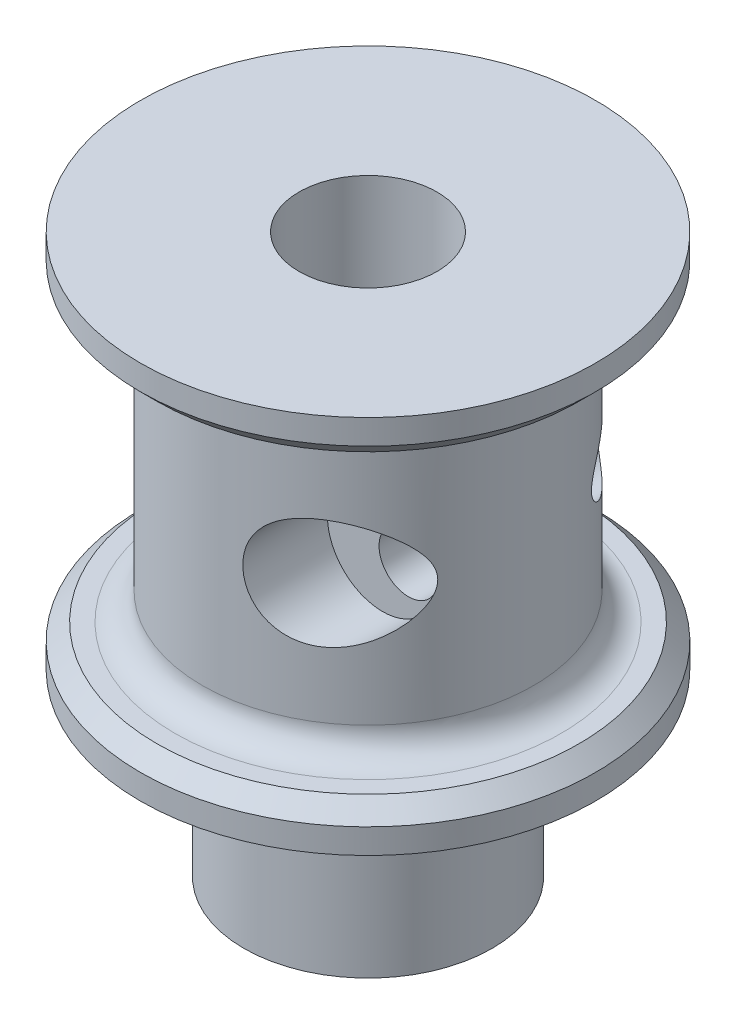
SolidWorks part; units mm, degrees
ref_plane "Front Plane" through (0, 0, 0) normal (0, 0, 1) x (1, 0, 0)
ref_plane "Top Plane" through (0, 0, 0) normal (0, 1, 0) x (1, 0, 0)
ref_plane "Right Plane" through (0, 0, 0) normal (1, 0, 0) x (0, 0, -1)
sketch "Sketch1" plane through (0, 0, 0) normal (0, 0, 1) x (1, 0, 0)
  line L0 (0, 0) -> (14.2875, 0)
  line L1 (14.2875, 0) -> (14.2875, 20.6375)
  line L2 (14.2875, 20.6375) -> (26.1938, 20.6375)
  line L3 (26.1938, 20.6375) -> (26.1938, 25.4)
  line L4 (26.1938, 25.4) -> (19.05, 25.4)
  line L5 (19.05, 25.4) -> (19.05, 59.5312)
  line L6 (19.05, 59.5312) -> (26.1938, 59.5312)
  line L7 (26.1938, 59.5312) -> (26.1938, 64.2938)
  line L8 (26.1938, 64.2938) -> (0, 64.2938)
  line L9 (0, 64.2938) -> (0, 0)
  dimension "D1" = 14.2875
  dimension "D2" = 26.1937
  dimension "D3" = 19.05
  dimension "D4" = 4.7625
  dimension "D5" = 20.6375
  dimension "D6" = 43.6562
revolve "Revolve1" add sketch "Sketch1" angle 360 about L9
hole_wizard "#10-24 Tapped Hole1" positions "Sketch2" profile "Sketch3" tap size "#10-24" standard "ANSI Inch" end condition through all
sketch "Sketch2" plane through (0, 64.2938, 0) normal (0, 1, 0) x (1, 0, 0)
  point P0 (0, 0)
sketch "Sketch3" plane through (0, 64.2938, 0) normal (1, 0, 0) x (0, 0, 1)
  line L0 (0, 0) -> (0, 64.2938)
  line L1 (0, 64.2938) -> (1.8986, 64.2938)
  line L2 (1.8986, 64.2938) -> (1.8986, 0)
  line L5 (1.8986, 0) -> (0, 0)
  line L11 (0, -6.35) -> (0, 107.95) construction
  dimension "Thru Tap Drill Dia." = 3.7973
  dimension "Thru Tap Drill Depth" = 64.2938
cosmetic thread "Hole Thread1" parameters "D2"=4.826
chamfer "Chamfer1" distance 1.905 angle 45 2 edges at (0, 25.4, 26.1938) (0, 59.5312, 26.1938)
fillet "Fillet1" radius 3.175 2 edges at (0, 59.5312, 19.05) (0, 25.4, 19.05)
sketch "Sketch4" plane through (0, 64.2938, 0) normal (0, 1, 0) x (1, 0, 0)
  circle A0 centre (0, 0) radius 12.7
  dimension "D1" = 25.4
extrude "Cut-Extrude1" [suppressed] cut sketch "Sketch4" against normal offset from surface (38.8937 mm away) 4.7625
sketch "Sketch5" plane through (0, 64.2938, 0) normal (0, 1, 0) x (1, 0, 0)
  circle A0 centre (0, 0) radius 7.9375
  dimension "D1" = 15.875
extrude "Cut-Extrude2" cut sketch "Sketch5" against normal offset from surface (56.6737 mm away) 7.62 up to face at (0, 0, 1.8986)
sketch "Sketch6" plane through (0, 0, 0) normal (0, 0, 1) x (1, 0, 0)
  line L0 (19.05, 56.3562) -> (19.05, 28.575)
  line L1 (-19.05, 28.575) -> (-19.05, 56.3562)
  line L2 (-19.05, 28.575) -> (-19.05, 56.3562)
  line L3 (19.05, 56.3562) -> (19.05, 28.575)
  circle A0 centre (13.4938, 42.4656) radius 3.3782
  point P3 (19.05, 42.4656)
  point P7 (19.05, 42.4656)
  point P8 (0, 0)
  dimension "D1" = 6.7564
  dimension "D2" = 5.5562
extrude "Cut-Extrude3" cut sketch "Sketch6" against normal through all both and the other way through all contours A0 region at (13.4938, 42.4656, 0)
ref_axis "Axis1" through (13.4938, 42.4656, -16.5609) along (0, 0, 1)
ref_plane "Plane1" through (0, 42.4656, 0) normal (0, 1, 0) x (1, 0, 0)
sketch "Sketch8" plane through (0, 42.4656, 0) normal (0, 1, 0) x (1, 0, 0)
  arc A0 (10.1156, -16.1424) -> (16.872, -8.8453) centre (0, 0) ccw construction
  arc A1 (10.1156, -16.1424) -> (16.872, -8.8453) centre (0, 0) ccw
sketch "Sketch7" plane through (0, 0, 0) normal (0, 0, 1) x (1, 0, 0)
  circle A0 centre (10.522, 42.4656) radius 6.35
  circle A1 centre (13.4938, 42.4656) radius 3.3782 construction
  point P3 (13.4938, 42.4656)
  point P6 (13.4938, 42.4656)
  dimension "D1" = 12.7
extrude "Cut-Extrude4" cut sketch "Sketch7" along normal through all from vertex contours A0 starting at point (16.872, 42.4656, 8.8453)
